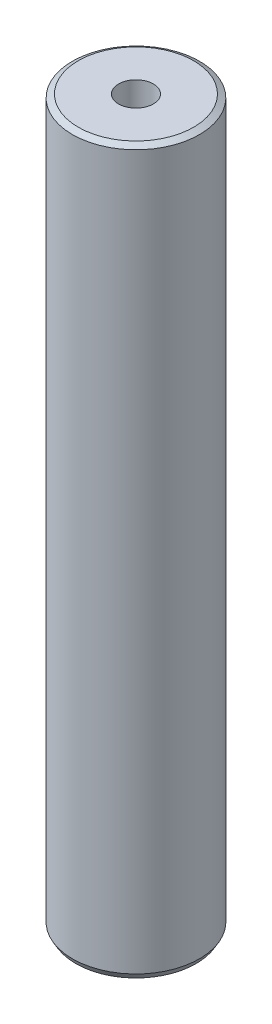
SolidWorks part; units mm, degrees
ref_plane "Front Plane" through (0, 0, 0) normal (0, 0, 1) x (1, 0, 0)
ref_plane "Top Plane" through (0, 0, 0) normal (0, 1, 0) x (1, 0, 0)
ref_plane "Right Plane" through (0, 0, 0) normal (1, 0, 0) x (0, 0, -1)
sketch "Sketch1" plane through (0, 0, 0) normal (0, 1, 0) x (1, 0, 0)
  circle A0 centre (0, 0) radius 12.5
  dimension "SHAFT_OD" = 25
extrude "Boss-Extrude1" add sketch "Sketch1" along normal blind 142.199
sketch "Sketch2" plane through (0, 0, 0) normal (0, 1, 0) x (1, 0, 0)
  circle A0 centre (0, 0) radius 3.419
  dimension "BORE_D" = 6.838
extrude "Cut-Extrude1" cut sketch "Sketch2" along normal through all
chamfer "Chamfer1" distance 0.6704 angle 60 2 edges at (0, 142.199, 12.5) (0, 0, 12.5) first distance on face at (0, 142.199, 12.5) first distance on face at (0, 0, 3.419)
